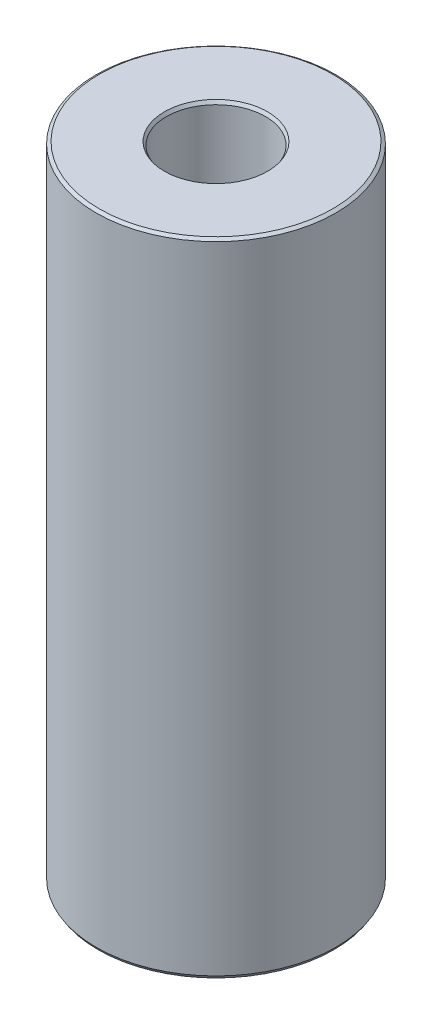
SolidWorks part; units mm, degrees
ref_plane "Front Plane" through (0, 0, 0) normal (0, 0, 1) x (1, 0, 0)
ref_plane "Top Plane" through (0, 0, 0) normal (0, 1, 0) x (1, 0, 0)
ref_plane "Right Plane" through (0, 0, 0) normal (1, 0, 0) x (0, 0, -1)
sketch "Sketch1" plane through (0, 0, 0) normal (0, 1, 0) x (1, 0, 0)
  circle A0 centre (0, 0) radius 25
  dimension "SLEEVE_OD" = 50
extrude "Boss-Extrude1" add sketch "Sketch1" along normal blind 133.76
sketch "Sketch2" plane through (0, 0, 0) normal (0, 1, 0) x (1, 0, 0)
  circle A0 centre (0, 0) radius 10.3444
  dimension "BORE_D" = 20.6888
extrude "Cut-Extrude1" cut sketch "Sketch2" along normal through all
chamfer "Chamfer1" distance 0.4186 angle 57.568 4 edges at (0, 133.76, 10.3444) (0, 0, 10.3444) (0, 0, 25) (0, 133.76, 25) first distance on face at (0, 133.76, 10.3444) first distance on face at (0, 0, 10.3444) first distance on face at (0, 133.76, 25)
